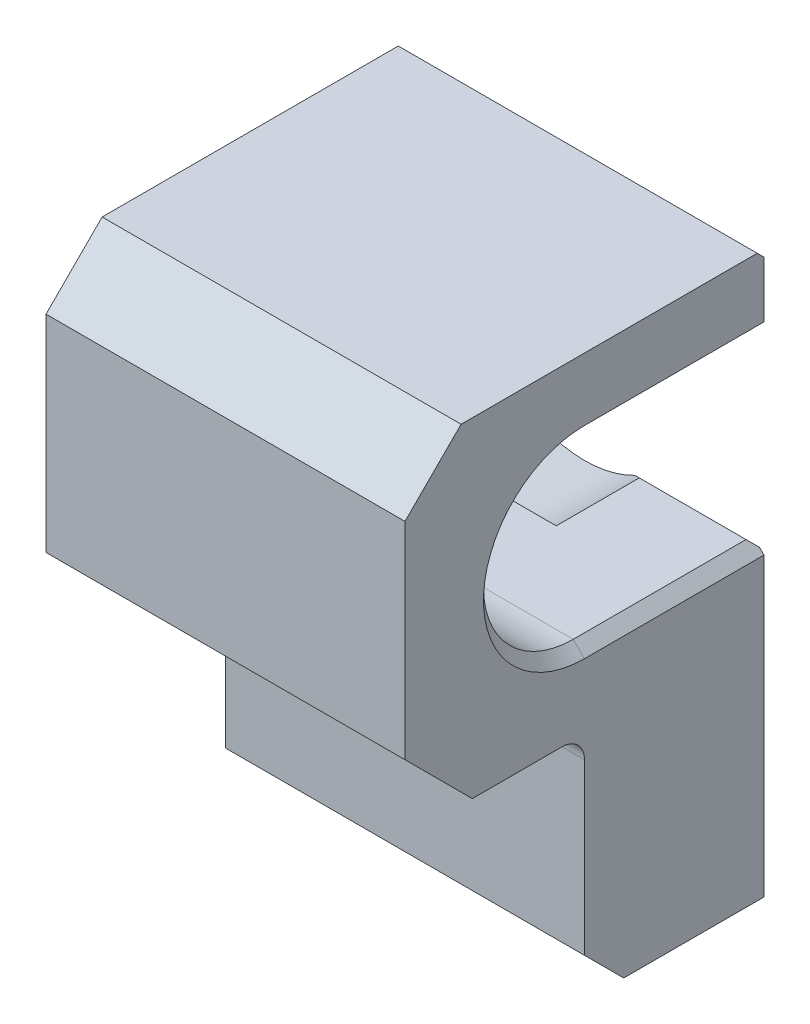
SolidWorks part; units mm, degrees
material "6061-T6 (SS)"
ref_plane "Front Plane" through (0, 0, 0) normal (0, 0, 1) x (1, 0, 0)
ref_plane "Top Plane" through (0, 0, 0) normal (0, 1, 0) x (1, 0, 0)
ref_plane "Right Plane" through (0, 0, 0) normal (1, 0, 0) x (0, 0, -1)
sketch "Sketch2" plane through (0, 0, 0) normal (1, 0, 0) x (0, 0, -1)
  line L0 (0, -0.3) -> (0, -13.7)
  line L1 (0, -13.7) -> (-6.25, -13.7)
  line L2 (-6.25, -13.7) -> (-8, -11.95)
  line L3 (-8, -11.95) -> (-8, -4.4)
  line L4 (-9, -3.4) -> (-13, -3.4)
  line L5 (-13, -3.4) -> (-16, -0.4)
  line L6 (-16, -0.4) -> (-16, 8.8)
  line L7 (-16, 8.8) -> (-13.5, 11.3)
  line L8 (-13.5, 11.3) -> (-0.3, 11.3)
  line L9 (0, 11) -> (0, 8.3)
  line L10 (-0.3, 8) -> (-8, 8)
  line L11 (-0.3, 0) -> (-8, 0)
  line L12 (0, -0.3) -> (-0.3, 0)
  line L13 (0, 8.3) -> (-0.3, 8)
  line L14 (-0.3, 11.3) -> (0, 11)
  arc A0 (-8, 8) -> (-8, 0) centre (-8, 4) ccw
  arc A1 (-8, -4.4) -> (-9, -3.4) centre (-9, -4.4) ccw
  point P0 (0, 0)
  point P11 (0, 11.3)
  point P12 (0, 8)
  dimension "D7" = 1
  dimension "D9" = 4
  dimension "D1" = 13.7
  dimension "D2" = 8
  dimension "D3" = 45
  dimension "D4" = 45
  dimension "D5" = 45
  dimension "D6" = 6.25
  dimension "D8" = 25
  dimension "D10" = 8
  dimension "D11" = 8
  dimension "D12" = 8
  dimension "D13" = 5
  dimension "D14" = 14.7
  dimension "D15" = 3.3
  dimension "D16" = 3.4
  dimension "D17" = 13.5
  dimension "D18" = 9.2
extrude "Boss-Extrude1" add sketch "Sketch2" along normal blind 8 and the other way blind 8
sketch "Sketch3" plane through (0, 0, 0) normal (0, 0, -1) x (-1, 0, 0)
  line L0 (0, 0) -> (0, 8) construction
  line L1 (8, 8) -> (-8, 8) construction
  circle A0 centre (0, 4) radius 4.85
  dimension "D1" = 9.7
extrude "Cut-Extrude1" cut sketch "Sketch3" against normal blind 4
sketch "Sketch6" plane through (0, 0, 0) normal (0, 0, -1) x (-1, 0, 0)
  line L0 (0, -13.7) -> (0, -6.7) construction
  line L1 (8, -13.7) -> (-8, -13.7) construction
  point P1 (0, -6.7)
  point P10 (0, -6.7)
  dimension "D1" = 7
hole_wizard "Tap Drill for 1/4-20 Tap1" positions "Sketch6" profile "Sketch7" hole size "1/4-20" standard "ANSI Inch"
sketch "Sketch7" plane through (0, -6.7, 0) normal (1, 0, 0) x (0, 1, 0)
  line L0 (0, 0) -> (0, 7)
  line L1 (0, 7) -> (2.5527, 5.4662)
  line L2 (2.5527, 5.4662) -> (2.5527, 0)
  line L5 (2.5527, 0) -> (0, 0)
  line L10 (0, 7) -> (-2.5527, 5.4662) construction
  line L11 (0, -6.35) -> (0, 107.95) construction
  dimension "Hole Dia." = 5.1054
  dimension "Hole Depth" = 7
  dimension "Drill Angle" = 118
chamfer "Chamfer1" distance 1 angle 45 1 edges at (0, -4.1473, 0)
thread "Thread1" pitch 1.27 method cut profile "Thread Profile1" start angle 0, offset 2, length 0, pitch 1.27, diameter 5.1054
ref_plane "Plane1" through (2.5527, -6.7, -1) normal (0, -1, 0) x (1, 0, 0)
sketch "Thread Profile1" plane through (2.5527, -6.7, -1) normal (0, -1, 0) x (1, 0, 0)
  line L0 (0, 0) -> (0, 1.27) construction
  line L1 (0, 0) -> (0.6874, 0.3969)
  line L2 (0.6874, 0.3969) -> (0.6874, 0.5556)
  line L3 (0.6874, 0.5556) -> (0, 0.9525)
  line L4 (0.6874, 0.4762) -> (0, 0.4762) construction
  line L11 (0, 0) -> (0, 0.9525)
  point P2 (0, 0)
  dimension "Pitch" = 1.27
  dimension "Profile_Angle" = 60
  dimension "Profile_Land" = 0.1588
  dimension "Profile_Height" = 0.6874
chamfer "Chamfer2" distance 0.5 angle 45 6 edges at (-8, 0, 4.15) (-8, 8, 4.15) (-8, 4, 12) (8, 0, 4.15) (8, 8, 4.15) (8, 4, 12)
